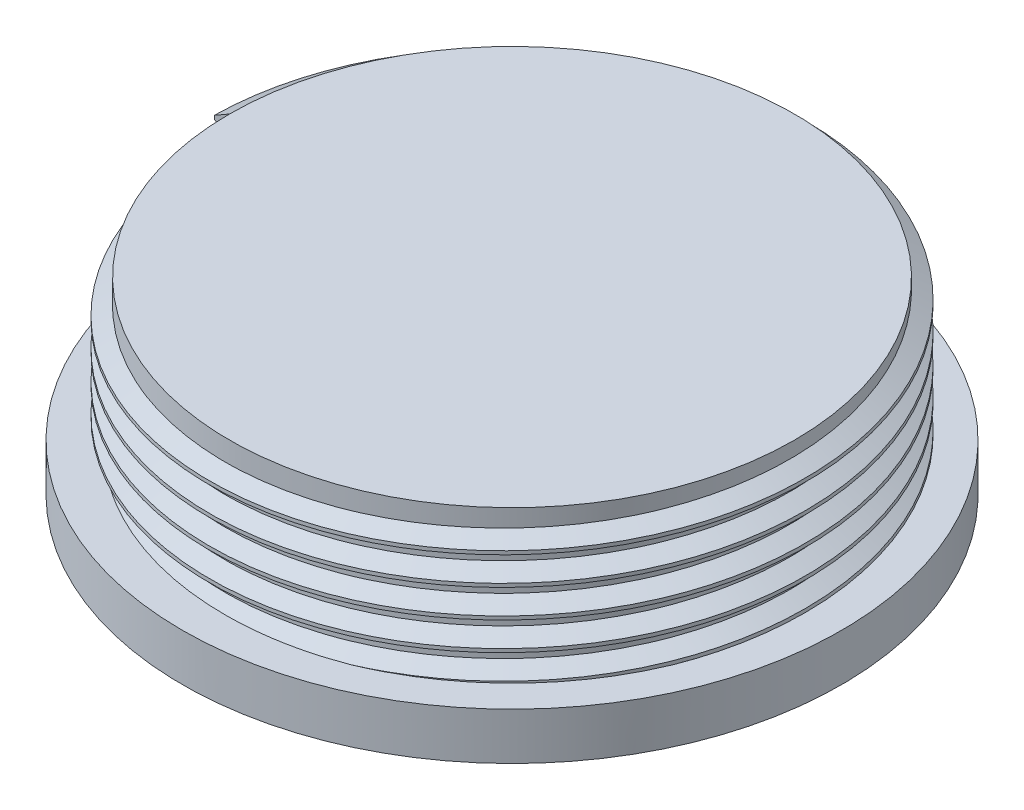
SolidWorks part; units mm, degrees
ref_plane "Front Plane" through (0, 0, 0) normal (0, 0, 1) x (1, 0, 0)
ref_plane "Top Plane" through (0, 0, 0) normal (0, 1, 0) x (1, 0, 0)
ref_plane "Right Plane" through (0, 0, 0) normal (1, 0, 0) x (0, 0, -1)
sketch "Sketch1" plane through (0, 0, 0) normal (0, 1, 0) x (1, 0, 0)
  circle A0 centre (0, 0) radius 50
  dimension "D1" = 100
extrude "Boss-Extrude1" add sketch "Sketch1" along normal blind 2.5
sketch "Sketch2" plane through (0, 2.5, 0) normal (0, 1, 0) x (1, 0, 0)
  circle A0 centre (0, 0) radius 15
  dimension "D1" = 30
extrude "Boss-Extrude2" add sketch "Sketch2" along normal blind 7.5
thread "Thread1" pitch 1.5 method extrude profile "Thread Profile1" start angle 0, offset 0, length 7.5, pitch 1.5, diameter 30
ref_plane "Plane1" through (-15, 10, 0) normal (0, 0, 1) x (-1, 0, 0)
sketch "Thread Profile1" plane through (-15, 10, 0) normal (0, 0, 1) x (-1, 0, 0)
  line L0 (0, 0) -> (0, 1.5) construction
  line L1 (0, 0) -> (0.8119, 0.4687)
  line L2 (0.8119, 0.4687) -> (0.8119, 0.6562)
  line L3 (0.8119, 0.6562) -> (0, 1.125)
  line L4 (0.8119, 0.5625) -> (0, 0.5625) construction
  line L11 (0, 0) -> (0, 1.125)
  point P2 (0, 0)
  dimension "Pitch" = 1.5
  dimension "Profile_Angle" = 60
  dimension "Profile_Land" = 0.1875
  dimension "Profile_Height" = 0.8119
sketch "Sketch3" plane through (0, 0, 0) normal (0, -1, 0) x (-1, 0, 0)
  circle A0 centre (0, 0) radius 17.5
  dimension "D1" = 35
extrude "Cut-Extrude1" cut sketch "Sketch3" against normal blind 10 flip side to cut
